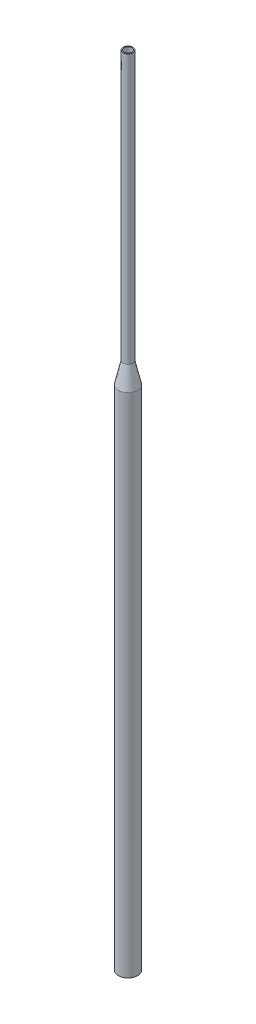
SolidWorks part; units mm, degrees
ref_plane "Plan de face" through (0, 0, 0) normal (0, 0, 1) x (1, 0, 0)
ref_plane "Plan de dessus" through (0, 0, 0) normal (0, 1, 0) x (1, 0, 0)
ref_plane "Plan de droite" through (0, 0, 0) normal (1, 0, 0) x (0, 0, -1)
sketch "Esquisse1" plane through (0, 0, 0) normal (0, 1, 0) x (1, 0, 0)
  circle A0 centre (0, 0) radius 5
  dimension "D1" = 10
extrude "Boss.-Extru.1" add sketch "Esquisse1" along normal blind 820
sketch "Esquisse2" plane through (0, 0, 0) normal (0, 1, 0) x (1, 0, 0)
  circle A0 centre (0, 0) radius 10
  dimension "D1" = 20
extrude "Boss.-Extru.2" add sketch "Esquisse2" along normal blind 500
chamfer "Chanfrein1" distance 10 angle 77 1 edges at (0, 500, 5) first distance on face at (0, 500, 5)
sketch "Esquisse3" plane through (0, 820, 0) normal (0, 1, 0) x (1, 0, 0)
  circle A0 centre (0, 0) radius 4
  dimension "D1" = 8
extrude "Enlèv. mat.-Extru.1" cut sketch "Esquisse3" against normal through all
